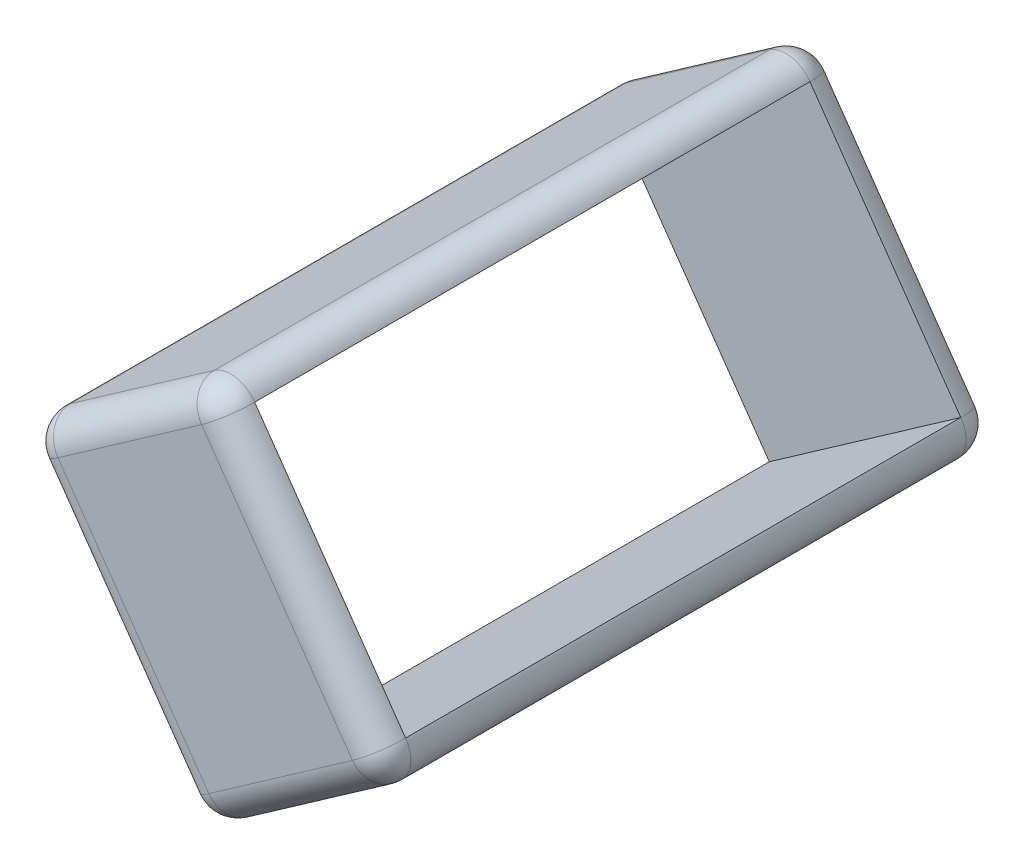
SolidWorks part; units mm, degrees
ref_plane "Front" through (0, 0, 0) normal (0, 0, 1) x (1, 0, 0)
ref_plane "Top" through (0, 0, 0) normal (0, 1, 0) x (1, 0, 0)
ref_plane "Right" through (0, 0, 0) normal (1, 0, 0) x (0, 0, -1)
sketch "Sketch1" plane through (0, 0, 0) normal (0, 0, 1) x (1, 0, 0)
  line L0 (0, -21) -> (24.6889, -56.2594) construction
  line L1 (0, -21) -> (44.9807, -21) construction
  line L2 (17.3721, -52.7838) -> (11.0628, -43.7731)
  line L3 (11.0628, -43.7731) -> (17.616, -39.1845)
  line L4 (17.616, -39.1845) -> (23.9254, -48.1952)
  line L5 (23.9254, -48.1952) -> (17.3721, -52.7838)
  circle A0 centre (0, -21) radius 35 construction
  point P5 (14.3394, -41.4788)
  dimension "D1" = 55
  dimension "D2" = 8
  dimension "D3" = 11
  dimension "D4" = 25
extrude "Base-Extrude" add sketch "Sketch1" along normal mid plane 21
fillet "Fillet1" radius 1 12 edges at (17.616, -39.1845, 0) (11.0628, -43.7731, 0) (14.2175, -48.2784, -10.5) (20.7707, -43.6898, -10.5) (14.3394, -41.4788, -10.5) (17.3721, -52.7838, 0) (23.9254, -48.1952, 0) (20.6488, -50.4895, -10.5) (20.7707, -43.6898, 10.5) (20.6488, -50.4895, 10.5) (14.2175, -48.2784, 10.5) (14.3394, -41.4788, 10.5)
shell "Shell1" thickness 1 removed face at (20.7707, -43.6898, 0) removed face at (14.2175, -48.2784, 0)
